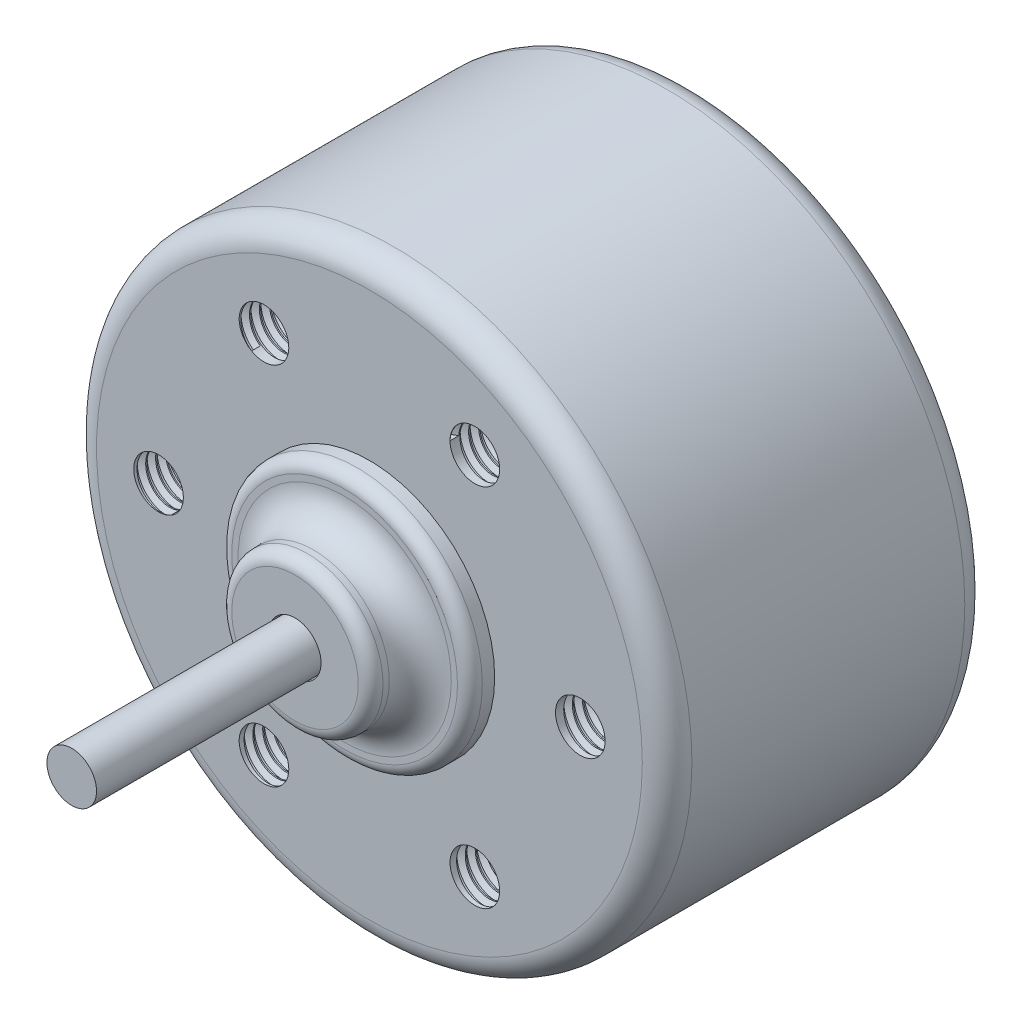
SolidWorks part; units mm, degrees
ref_plane "Front Plane" through (0, 0, 0) normal (0, 0, 1) x (1, 0, 0)
ref_plane "Top Plane" through (0, 0, 0) normal (0, 1, 0) x (1, 0, 0)
ref_plane "Right Plane" through (0, 0, 0) normal (1, 0, 0) x (0, 0, -1)
sketch "Sketch1" plane through (0, 0, 0) normal (0, 0, 1) x (1, 0, 0)
  circle A0 centre (0, 0) radius 12
  dimension "D1" = 24
extrude "Housing" add sketch "Sketch1" along normal mid plane 13
sketch "Sketch2" plane through (0, 0, 6.5) normal (0, 0, 1) x (1, 0, 0)
  circle A0 centre (0, 0) radius 1
  dimension "D1" = 2
extrude "Shaft" add sketch "Sketch2" along normal blind 12
fillet "Fillet1" radius 1 2 edges at (12, 0, -6.5) (12, 0, 6.5)
sketch "Sketch16" plane through (0, 0, 0) normal (0, 1, 0) x (1, 0, 0)
  line L0 (0, -19.3529) -> (0, 7.1196) construction
  line L1 (-11, -6.5) -> (11, -6.5) construction
  line L2 (-5.05, -6.5) -> (-1.05, -6.5)
  line L3 (-1.05, -6.5) -> (-1.05, -9.5)
  line L4 (-1.05, -9.5) -> (-2.55, -9.5)
  line L5 (-3.05, -9) -> (-3.05, -8.75)
  line L6 (-4.3, -7.5) -> (-4.55, -7.5)
  line L7 (-5.05, -7) -> (-5.05, -6.5)
  line L8 (-1, -6.5) -> (-1, -18.5) construction
  arc A0 (-3.05, -8.75) -> (-4.3, -7.5) centre (-4.3, -8.75) ccw
  arc A2 (-2.55, -9.5) -> (-3.05, -9) centre (-2.55, -9) cw
  arc A3 (-4.55, -7.5) -> (-5.05, -7) centre (-4.55, -7) cw
  point P15 (-3.05, -7.5)
  point P18 (-1.05, -9.5)
  point P21 (-3.05, -9.5)
  point P24 (-5.05, -7.5)
  dimension "D6" = 1.25
  dimension "D7" = 0.5
  dimension "D1" = 0.05
  dimension "D2" = 2
  dimension "D3" = 1
  dimension "D4" = 2
  dimension "D5" = 2
revolve "ShaftSupport" add sketch "Sketch16" angle 360 about L0
fillet "Fillet2" [suppressed] radius 2
sketch "ScrewHole" plane through (0, 0, 6.5) normal (0, 0, 1) x (1, 0, 0)
  line L0 (0, 0) -> (18.7448, 0) construction
  line L1 (0, 0) -> (9.5108, 16.4733) construction
  point P4 (4.25, 7.3612)
  dimension "D1" = 60
  dimension "D2" = 8.5
hole_wizard "Ø2.0mm Dowel Hole4" positions "3DSketch2" profile "Sketch12" hole size "Ø2.0" standard "ANSI Metric"
sketch3d "3DSketch2"
  point P1 (4.25, 7.3612, 6.5)
sketch "Sketch12" plane through (4.25, 7.3612, 6.5) normal (1, 0, 0) x (0, -1, 0)
  line L0 (0, 0) -> (0, 6.6009)
  line L1 (0, 6.6009) -> (1, 6)
  line L2 (1, 6) -> (1, 0)
  line L5 (1, 0) -> (0, 0)
  line L10 (0, 6.6009) -> (-1, 6) construction
  line L11 (0, -6.35) -> (0, 107.95) construction
  dimension "Hole Dia." = 2
  dimension "Hole Depth" = 6
  dimension "Drill Angle" = 118
thread "Thread2" pitch 0.4 method cut profile "Thread Profile2" start angle 0, offset 0, length 0, pitch 0.4, diameter 2
ref_plane "Plane2" through (3.25, 7.3612, 6.5) normal (0, -1, 0) x (-1, 0, 0)
sketch "Thread Profile2" plane through (3.25, 7.3612, 6.5) normal (0, -1, 0) x (-1, 0, 0)
  line L0 (0, 0) -> (0, 0.4) construction
  line L11 (0, 0.35) -> (0, 0)
  line L12 (0, 0) -> (0.2165, 0.125)
  line L13 (0.2165, 0.125) -> (0.2165, 0.225)
  line L15 (0.2165, 0.225) -> (0, 0.35)
  line L17 (0.2165, 0.175) -> (0, 0.175) construction
  point P3 (0, 0)
  dimension "Pitch" = 0.4
  dimension "Profile_Angle" = 60
  dimension "Profile_Land" = 0.1
  dimension "Profile_Height" = 0.2165
pattern_circular "CirPattern1" count 6 over 360 about axis through (0, 0, 6.5) along (0, 0, 1) of "Thread2", "Ø2.0mm Dowel Hole4"
